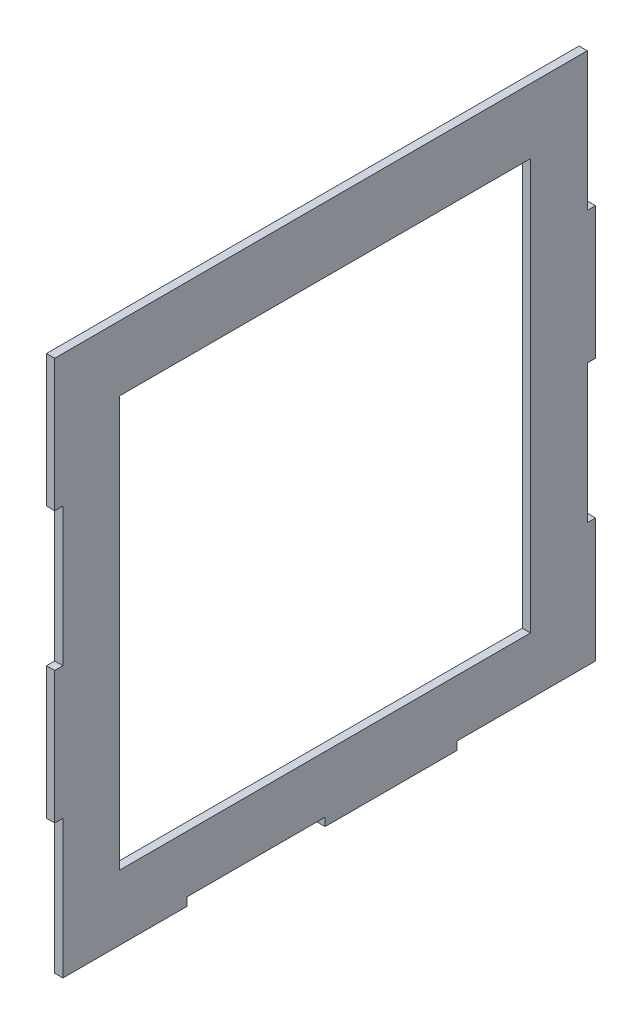
SolidWorks part; units mm, degrees
ref_plane "Front Plane" through (0, 0, 0) normal (0, 0, 1) x (1, 0, 0)
ref_plane "Top Plane" through (0, 0, 0) normal (0, 1, 0) x (1, 0, 0)
ref_plane "Right Plane" through (0, 0, 0) normal (1, 0, 0) x (0, 0, -1)
sketch "Sketch2" plane through (0, 0, 0) normal (1, 0, 0) x (0, 0, -1)
  line L1 (-197.5, -197.5) -> (197.5, -197.5)
  line L2 (-197.5, -197.5) -> (-197.5, 197.5)
  line L3 (-197.5, 197.5) -> (197.5, 197.5)
  line L4 (197.5, -197.5) -> (197.5, 197.5)
  line L5 (-197.5, -197.5) -> (197.5, 197.5) construction
  line L6 (-197.5, 197.5) -> (197.5, -197.5) construction
  line L7 (-150, -150) -> (150, -150)
  line L8 (-150, -150) -> (-150, 150)
  line L9 (-150, 150) -> (150, 150)
  line L10 (150, -150) -> (150, 150)
  line L11 (-150, -150) -> (150, 150) construction
  line L12 (-150, 150) -> (150, -150) construction
  line L13 (197.5, -197.5) -> (96.5, -197.5)
  line L14 (197.5, -197.5) -> (197.5, -191.5)
  line L15 (197.5, -191.5) -> (96.5, -191.5)
  line L16 (96.5, -197.5) -> (96.5, -191.5)
  line L17 (0, -197.5) -> (-101, -197.5)
  line L18 (0, -197.5) -> (0, -191.5)
  line L19 (0, -191.5) -> (-101, -191.5)
  line L20 (-101, -197.5) -> (-101, -191.5)
  line L21 (-197.5, -197.5) -> (-191.5, -197.5)
  line L22 (-197.5, -197.5) -> (-197.5, -96.5)
  line L23 (-197.5, -96.5) -> (-191.5, -96.5)
  line L24 (-191.5, -197.5) -> (-191.5, -96.5)
  line L25 (-197.5, 0) -> (-191.5, 0)
  line L26 (-197.5, 0) -> (-197.5, 101)
  line L27 (-197.5, 101) -> (-191.5, 101)
  line L28 (-191.5, 0) -> (-191.5, 101)
  line L29 (197.5, 197.5) -> (191.5, 197.5)
  line L30 (197.5, 197.5) -> (197.5, 96.5)
  line L31 (197.5, 96.5) -> (191.5, 96.5)
  line L32 (191.5, 197.5) -> (191.5, 96.5)
  line L33 (197.5, 0) -> (191.5, 0)
  line L34 (197.5, 0) -> (197.5, -101)
  line L35 (197.5, -101) -> (191.5, -101)
  line L36 (191.5, 0) -> (191.5, -101)
  point P0 (0, 0)
  point P6 (0, 0)
  dimension "D1" = 395
  dimension "D2" = 300
  dimension "D3" = 101
  dimension "D4" = 6
extrude "Boss-Extrude2" add sketch "Sketch2" along normal blind 6 contours L36 L33 L4 L31 L32 L3 L2 L27 L28 L25 L23 L24 L1 L20 L19 L18 L16 L15 L35 L10 L7 L8 L9 region at (0, -147, 185.9139)
